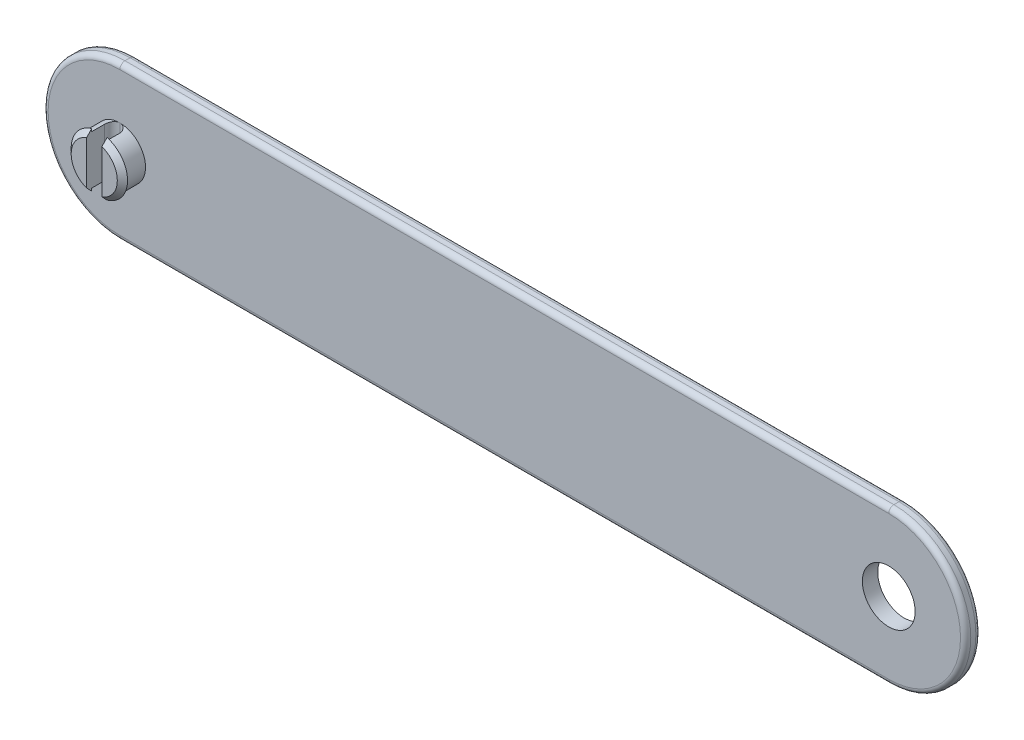
SolidWorks part; units mm, degrees
ref_plane "前视基准面" through (0, 0, 0) normal (0, 0, 1) x (1, 0, 0)
ref_plane "上视基准面" through (0, 0, 0) normal (0, 1, 0) x (1, 0, 0)
ref_plane "右视基准面" through (0, 0, 0) normal (1, 0, 0) x (0, 0, -1)
sketch "草图1" plane through (0, 0, 0) normal (0, 0, 1) x (1, 0, 0)
  line L0 (0, 0) -> (150, 0) construction
  line L1 (0, 15) -> (150, 15)
  line L2 (0, -15) -> (150, -15)
  arc A0 (0, 15) -> (0, -15) centre (0, 0) ccw
  arc A1 (150, -15) -> (150, 15) centre (150, 0) ccw
  circle A2 centre (150, 0) radius 5.15
  point P3 (75, 0)
  dimension "D2" = 15
  dimension "D3" = 10.3
  dimension "D1" = 150
extrude "凸台-拉伸1" add sketch "草图1" along normal blind 3 contours L1 A1 L2 A0
sketch "草图2" plane through (0, 0, 3) normal (0, 0, 1) x (1, 0, 0)
  line L2 (-1.5, 4.7697) -> (-1.5, -4.7697)
  line L4 (1.5, 4.7697) -> (1.5, -4.7697)
  arc A0 (-1.5, 4.7697) -> (-1.5, -4.7697) centre (0, 0) ccw
  arc A1 (1.5, -4.7697) -> (1.5, 4.7697) centre (0, 0) ccw
  dimension "D1" = 10
  dimension "D2" = 3
extrude "凸台-拉伸2" add sketch "草图2" along normal blind 4
sketch "草图5" plane through (0, 0, 7) normal (0, 0, 1) x (1, 0, 0)
  line L2 (-1.5, 5.2915) -> (-1.5, -5.2915)
  line L4 (1.5, 5.2915) -> (1.5, -5.2915)
  arc A0 (-1.5, 5.2915) -> (-1.5, -5.2915) centre (0, 0) ccw
  arc A1 (1.5, -5.2915) -> (1.5, 5.2915) centre (0, 0) ccw
  dimension "D1" = 11
  dimension "D2" = 3
extrude "凸台-拉伸3" add sketch "草图5" along normal blind 1
chamfer "倒角1" distance 1 angle 45 2 edges at (5.5, 0, 8) (-5.5, 0, 8)
extrude "切除-拉伸1" cut sketch "草图1<3>" along normal blind 5 contours A2 region at (150, 0, 0)
sketch "草图1<3>" plane through (0, 0, 0) normal (0, 0, 1) x (1, 0, 0) same geometry as "草图1"
fillet "圆角1" radius 1.5 2 edges at (1.5, 0, 3) (-1.5, 0, 3)
fillet "圆角2" radius 1 8 edges at (-15, 0, 0) (75, -15, 0) (165, 0, 0) (-15, 0, 3) (75, -15, 3) (165, 0, 3) (75, 15, 0) (75, 15, 3)
